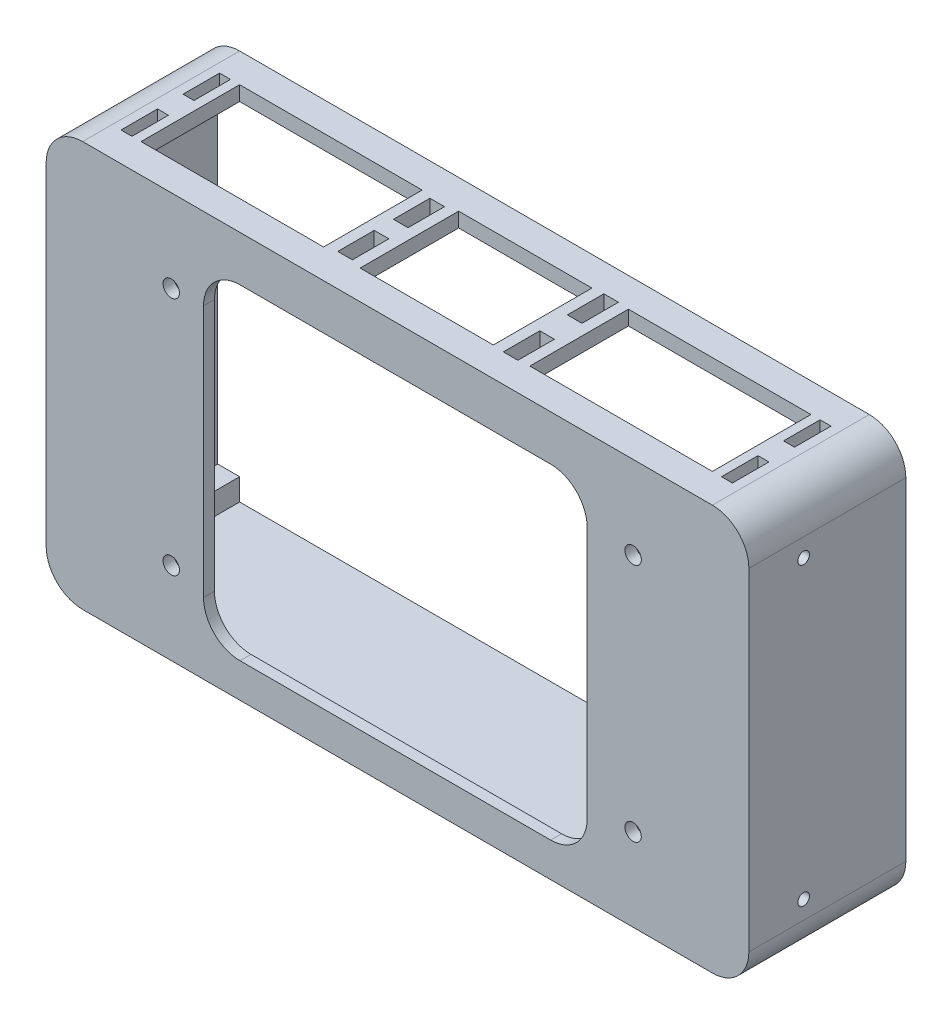
SolidWorks part; units mm, degrees
ref_plane "Front Plane" through (0, 0, 0) normal (0, 0, 1) x (1, 0, 0)
ref_plane "Top Plane" through (0, 0, 0) normal (0, 1, 0) x (1, 0, 0)
ref_plane "Right Plane" through (0, 0, 0) normal (1, 0, 0) x (0, 0, -1)
sketch "Sketch1" plane through (0, 0, 0) normal (0, 0, 1) x (1, 0, 0)
  line L0 (-99.8273, 155.9635) -> (-99.8273, 44.9635) construction
  line L1 (-13.5773, 155.9635) -> (-186.0773, 155.9635)
  line L2 (-3.5773, 145.9635) -> (-3.5773, 54.9635)
  line L3 (-13.5773, 44.9635) -> (-186.0773, 44.9635)
  line L4 (-196.0773, 145.9635) -> (-196.0773, 54.9635)
  line L5 (-99.8273, 100.4635) -> (-2.2558, 100.4635) construction
  line L7 (-57.8741, 143.5345) -> (-142.9734, 143.5345)
  line L8 (-47.8741, 133.5345) -> (-47.8741, 64.3568)
  line L9 (-57.8741, 54.3568) -> (-142.9734, 54.3568)
  line L10 (-152.9734, 133.5345) -> (-152.9734, 64.3568)
  arc A0 (-186.0773, 155.9635) -> (-196.0773, 145.9635) centre (-186.0773, 145.9635) ccw
  arc A1 (-196.0773, 54.9635) -> (-186.0773, 44.9635) centre (-186.0773, 54.9635) ccw
  arc A2 (-13.5773, 44.9635) -> (-3.5773, 54.9635) centre (-13.5773, 54.9635) ccw
  arc A3 (-3.5773, 145.9635) -> (-13.5773, 155.9635) centre (-13.5773, 145.9635) ccw
  circle A4 centre (-35.2921, 133.2897) radius 2.25
  circle A5 centre (-35.2976, 67.5999) radius 2.25
  circle A6 centre (-161.808, 67.58) radius 2.25
  circle A7 centre (-161.8084, 133.2885) radius 2.25
  arc A8 (-152.9734, 133.5345) -> (-142.9734, 143.5345) centre (-142.9734, 133.5345) cw
  arc A9 (-152.9734, 64.3568) -> (-142.9734, 54.3568) centre (-142.9734, 64.3568) ccw
  arc A10 (-57.8741, 54.3568) -> (-47.8741, 64.3568) centre (-57.8741, 64.3568) ccw
  arc A11 (-47.8741, 133.5345) -> (-57.8741, 143.5345) centre (-57.8741, 133.5345) ccw
  point P6 (-196.0773, 155.9635)
  point P11 (-3.5773, 44.9635)
  point P14 (-3.5773, 155.9635)
  dimension "D3" = 10
  dimension "D6" = 4.5
  dimension "D7" = 10
  dimension "D1" = 192.5
  dimension "D2" = 111
  dimension "D4" = 96.25
  dimension "D5" = 55.5
extrude "Boss-Extrude1" add sketch "Sketch1" against normal blind 3
sketch "Sketch3" plane through (0, 0, -3) normal (0, 0, -1) x (-1, 0, 0)
  line L0 (100.7329, 100.4635) -> (7.5773, 100.4635) construction
  line L2 (3.5773, 145.9635) -> (3.5773, 54.9635)
  line L4 (7.5773, 151.9635) -> (7.5773, 48.9635)
  line L5 (13.5773, 155.9635) -> (99.8273, 155.9635)
  line L7 (7.5773, 151.9635) -> (99.8273, 151.9635)
  line L9 (99.8273, 151.9635) -> (99.8273, 48.9635) construction
  line L11 (186.0773, 155.9635) -> (99.8273, 155.9635)
  line L12 (3.5773, 100.4635) -> (-65.7899, 100.4635) construction
  line L15 (192.0773, 151.9635) -> (99.8273, 151.9635)
  line L16 (192.0773, 151.9635) -> (192.0773, 48.9635)
  line L18 (196.0773, 145.9635) -> (196.0773, 54.9635)
  line L19 (186.0773, 44.9635) -> (99.8273, 44.9635)
  line L21 (192.0773, 48.9635) -> (99.8273, 48.9635)
  line L22 (13.5773, 44.9635) -> (99.8273, 44.9635)
  line L24 (7.5773, 48.9635) -> (99.8273, 48.9635)
  line L25 (99.8273, 44.9635) -> (99.8273, 33.155) construction
  arc A0 (13.5773, 155.9635) -> (3.5773, 145.9635) centre (13.5773, 145.9635) ccw
  arc A1 (186.0773, 155.9635) -> (196.0773, 145.9635) centre (186.0773, 145.9635) cw
  arc A2 (186.0773, 44.9635) -> (196.0773, 54.9635) centre (186.0773, 54.9635) ccw
  arc A3 (13.5773, 44.9635) -> (3.5773, 54.9635) centre (13.5773, 54.9635) cw
  dimension "D1" = 10
  dimension "D2" = 4
  dimension "D3" = 4
extrude "Boss-Extrude3" add sketch "Sketch3" along normal blind 40
sketch "Sketch4" plane through (0, 0, -43) normal (0, 0, -1) x (-1, 0, 0)
  line L0 (99.8273, 151.9635) -> (99.8273, 41.5457) construction
  line L1 (7.5773, 151.9635) -> (13.5773, 151.9635)
  line L2 (7.5773, 151.9635) -> (7.5773, 145.9635)
  line L3 (7.5773, 145.9635) -> (13.5773, 145.9635)
  line L4 (13.5773, 151.9635) -> (13.5773, 145.9635)
  line L5 (192.0773, 151.9635) -> (7.5773, 151.9635) construction
  line L6 (99.8273, 96.7546) -> (145.1612, 96.7546) construction
  line L7 (192.0773, 145.9635) -> (186.0773, 145.9635)
  line L8 (186.0773, 151.9635) -> (186.0773, 145.9635)
  line L9 (192.0773, 151.9635) -> (186.0773, 151.9635)
  line L10 (192.0773, 151.9635) -> (192.0773, 145.9635)
  line L11 (192.0773, 54.9635) -> (186.0773, 54.9635)
  line L12 (7.5773, 48.9635) -> (13.5773, 48.9635)
  line L13 (7.5773, 48.9635) -> (7.5773, 54.9635)
  line L14 (7.5773, 54.9635) -> (13.5773, 54.9635)
  line L15 (13.5773, 48.9635) -> (13.5773, 54.9635)
  line L16 (186.0773, 48.9635) -> (186.0773, 54.9635)
  line L17 (192.0773, 48.9635) -> (186.0773, 48.9635)
  line L18 (192.0773, 48.9635) -> (192.0773, 54.9635)
  circle A0 centre (10.5773, 148.9635) radius 1.6
  circle A1 centre (189.0773, 148.9635) radius 1.6
  circle A2 centre (10.5773, 51.9635) radius 1.6
  circle A3 centre (189.0773, 51.9635) radius 1.6
  dimension "D3" = 3
  dimension "D5" = 3.2
  dimension "D9" = 3
  dimension "D10" = 3.2
  dimension "D1" = 6
  dimension "D2" = 6
  dimension "D4" = 3
  dimension "D6" = 6
  dimension "D7" = 6
  dimension "D8" = 3
extrude "Boss-Extrude4" add sketch "Sketch4" against normal blind 10
sketch "Sketch5" plane through (0, 0, -33) normal (0, 0, 1) x (1, 0, 0)
  line L0 (-99.8273, 151.9635) -> (-99.8273, 41.5457) construction
  line L1 (-192.0773, 151.9635) -> (-186.0773, 151.9635)
  line L2 (-192.0773, 151.9635) -> (-192.0773, 145.9635)
  line L3 (-192.0773, 145.9635) -> (-186.0773, 145.9635)
  line L4 (-186.0773, 151.9635) -> (-186.0773, 145.9635)
  line L5 (-192.0773, 54.9635) -> (-186.0773, 54.9635)
  line L6 (-192.0773, 54.9635) -> (-192.0773, 48.9635)
  line L7 (-192.0773, 48.9635) -> (-186.0773, 48.9635)
  line L8 (-186.0773, 54.9635) -> (-186.0773, 48.9635)
  line L9 (-13.5773, 54.9635) -> (-13.5773, 48.9635)
  line L10 (-7.5773, 48.9635) -> (-13.5773, 48.9635)
  line L11 (-7.5773, 54.9635) -> (-7.5773, 48.9635)
  line L12 (-7.5773, 54.9635) -> (-13.5773, 54.9635)
  line L13 (-7.5773, 145.9635) -> (-13.5773, 145.9635)
  line L14 (-7.5773, 151.9635) -> (-7.5773, 145.9635)
  line L15 (-7.5773, 151.9635) -> (-13.5773, 151.9635)
  line L16 (-13.5773, 151.9635) -> (-13.5773, 145.9635)
extrude "Boss-Extrude5" add sketch "Sketch5" along normal blind 2
fillet "Fillet3" radius 10 4 edges at (-192.0773, 148.9635, -31) (-192.0773, 51.9635, -31) (-7.5773, 51.9635, -31) (-7.5773, 148.9635, -31)
sketch "Sketch6" plane through (0, 155.9635, 0) normal (0, 1, 0) x (1, 0, 0)
  line L0 (-186.0773, 43) -> (-13.5773, 43) construction
  line L1 (-178.0773, 35) -> (-128.0773, 35)
  line L2 (-178.0773, 35) -> (-178.0773, 8)
  line L3 (-178.0773, 8) -> (-128.0773, 8)
  line L4 (-128.0773, 35) -> (-128.0773, 8)
  line L5 (-118.0773, 35) -> (-81.5773, 35)
  line L6 (-118.0773, 35) -> (-118.0773, 8)
  line L7 (-118.0773, 8) -> (-81.5773, 8)
  line L8 (-81.5773, 35) -> (-81.5773, 8)
  line L9 (-71.5773, 35) -> (-21.5773, 35)
  line L10 (-71.5773, 35) -> (-71.5773, 8)
  line L11 (-71.5773, 8) -> (-21.5773, 8)
  line L12 (-21.5773, 35) -> (-21.5773, 8)
  line L13 (-13.5773, 0) -> (-186.0773, 0) construction
  line L14 (-186.0773, 43) -> (-186.0773, 0) construction
  line L16 (-13.5773, 43) -> (-13.5773, 0) construction
  dimension "D1" = 8
  dimension "D2" = 8
  dimension "D3" = 8
  dimension "D4" = 8
  dimension "D5" = 8
  dimension "D6" = 10
  dimension "D7" = 10
  dimension "D8" = 50
  dimension "D9" = 50
  dimension "D10" = 8
  dimension "D11" = 8
extrude "Cut-Extrude1" cut sketch "Sketch6" against normal blind 5
sketch "Sketch8" plane through (0, 155.9635, 0) normal (0, 1, 0) x (1, 0, 0)
  line L0 (-128.0773, 8) -> (-128.0773, 35) construction
  line L1 (-125.0773, 18.8763) -> (-121.0773, 18.8763)
  line L2 (-125.0773, 18.8763) -> (-125.0773, 8.8763)
  line L3 (-125.0773, 8.8763) -> (-121.0773, 8.8763)
  line L4 (-121.0773, 18.8763) -> (-121.0773, 8.8763)
  line L5 (-78.5773, 17.724) -> (-74.5773, 17.724)
  line L6 (-78.5773, 17.724) -> (-78.5773, 7.724)
  line L7 (-78.5773, 7.724) -> (-74.5773, 7.724)
  line L8 (-74.5773, 17.724) -> (-74.5773, 7.724)
  line L9 (-118.0773, 35) -> (-118.0773, 8) construction
  line L10 (-81.5773, 8) -> (-81.5773, 35) construction
  line L11 (-71.5773, 35) -> (-71.5773, 8) construction
  line L12 (-128.0773, 21.5) -> (-103.7607, 21.5) construction
  line L13 (-78.5773, 35.276) -> (-74.5773, 35.276)
  line L14 (-74.5773, 25.276) -> (-74.5773, 35.276)
  line L15 (-78.5773, 25.276) -> (-74.5773, 25.276)
  line L16 (-78.5773, 25.276) -> (-78.5773, 35.276)
  line L17 (-125.0773, 34.1237) -> (-121.0773, 34.1237)
  line L18 (-121.0773, 24.1237) -> (-121.0773, 34.1237)
  line L19 (-125.0773, 24.1237) -> (-121.0773, 24.1237)
  line L20 (-125.0773, 24.1237) -> (-125.0773, 34.1237)
  line L21 (-178.0773, 35) -> (-178.0773, 8) construction
  line L22 (-19.0773, 18) -> (-16.0773, 18)
  line L23 (-19.0773, 18) -> (-19.0773, 8)
  line L24 (-19.0773, 8) -> (-16.0773, 8)
  line L25 (-16.0773, 18) -> (-16.0773, 8)
  line L26 (-183.5773, 18) -> (-180.5773, 18)
  line L27 (-183.5773, 18) -> (-183.5773, 8)
  line L28 (-183.5773, 8) -> (-180.5773, 8)
  line L29 (-180.5773, 18) -> (-180.5773, 8)
  line L30 (-186.0773, 43) -> (-186.0773, 0) construction
  line L31 (-178.0773, 8) -> (-128.0773, 8) construction
  line L32 (-21.5773, 8) -> (-21.5773, 35) construction
  line L33 (-13.5773, 43) -> (-13.5773, 0) construction
  line L34 (-71.5773, 8) -> (-21.5773, 8) construction
  line L35 (-19.0773, 35) -> (-16.0773, 35)
  line L36 (-16.0773, 25) -> (-16.0773, 35)
  line L37 (-19.0773, 25) -> (-16.0773, 25)
  line L38 (-19.0773, 25) -> (-19.0773, 35)
  line L39 (-183.5773, 35) -> (-180.5773, 35)
  line L40 (-180.5773, 25) -> (-180.5773, 35)
  line L41 (-183.5773, 25) -> (-180.5773, 25)
  line L42 (-183.5773, 25) -> (-183.5773, 35)
  dimension "D1" = 3
  dimension "D2" = 3
  dimension "D3" = 3
  dimension "D4" = 3
  dimension "D5" = 10
  dimension "D6" = 10
  dimension "D7" = 2.5
  dimension "D8" = 2.5
  dimension "D9" = 0
  dimension "D10" = 10
  dimension "D11" = 2.5
  dimension "D12" = 2.5
  dimension "D13" = 0
  dimension "D14" = 10
extrude "Cut-Extrude2" cut sketch "Sketch8" against normal blind 5
sketch "Sketch9" plane through (-3.5773, 0, 0) normal (1, 0, 0) x (0, 0, -1)
  line L0 (43, 145.9635) -> (0, 145.9635) construction
  line L1 (43, 54.9635) -> (0, 54.9635) construction
  line L2 (0, 54.9635) -> (0, 145.9635) construction
  circle A0 centre (15, 140.9635) radius 1.6
  circle A1 centre (15, 59.9635) radius 1.6
  dimension "D3" = 15
  dimension "D4" = 15
  dimension "D5" = 3.2
  dimension "D1" = 5
  dimension "D2" = 5
extrude "Cut-Extrude3" cut sketch "Sketch9" against normal through all
